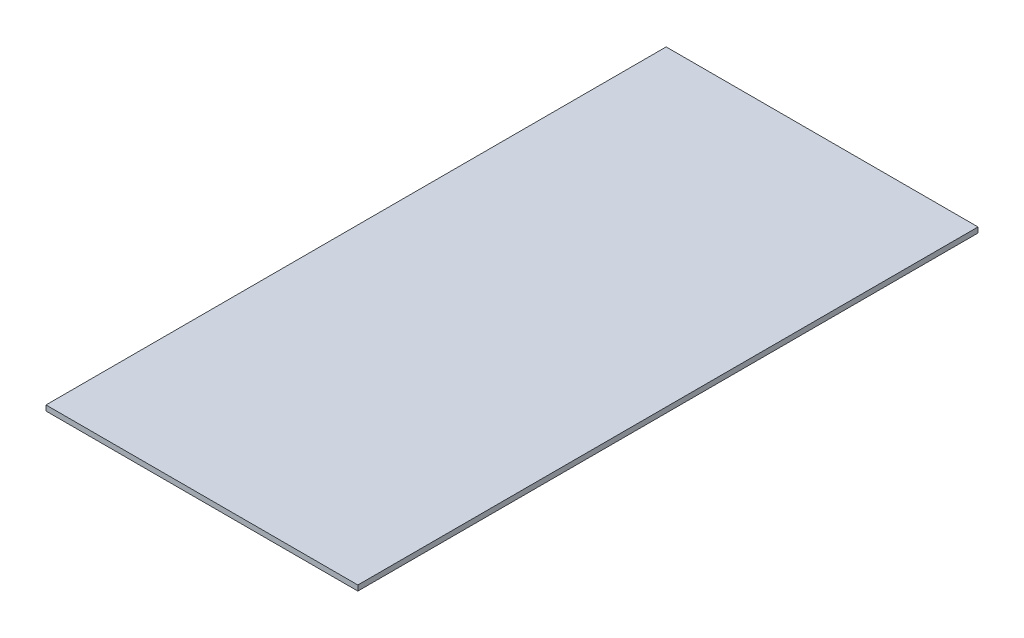
SolidWorks part; units mm, degrees
ref_plane "Front Plane" through (0, 0, 0) normal (0, 0, 1) x (1, 0, 0)
ref_plane "Top Plane" through (0, 0, 0) normal (0, 1, 0) x (1, 0, 0)
ref_plane "Right Plane" through (0, 0, 0) normal (1, 0, 0) x (0, 0, -1)
sketch "Sketch1" plane through (0, 0, 0) normal (0, 1, 0) x (1, 0, 0)
  line L1 (0, 0) -> (176, 0)
  line L2 (0, 0) -> (0, 350)
  line L3 (0, 350) -> (176, 350)
  line L4 (176, 0) -> (176, 350)
  dimension "D1" = 350
  dimension "D2" = 176
extrude "Boss-Extrude1" add sketch "Sketch1" along normal blind 3
sketch "Sketch2" plane through (0, 3, 0) normal (0, 1, 0) x (1, 0, 0)
  line L0 (176, 0) -> (176, 70)
  line L1 (176, 0) -> (176, 350) construction
  line L2 (176, 70) -> (88, 70)
  line L3 (176, 70) -> (176, 120)
  line L4 (176, 120) -> (176, 170)
  line L5 (176, 170) -> (176, 220)
  line L6 (176, 120) -> (88, 120)
  line L7 (176, 170) -> (88, 170)
  line L8 (176, 220) -> (88, 220)
  point P12 (0, 0)
